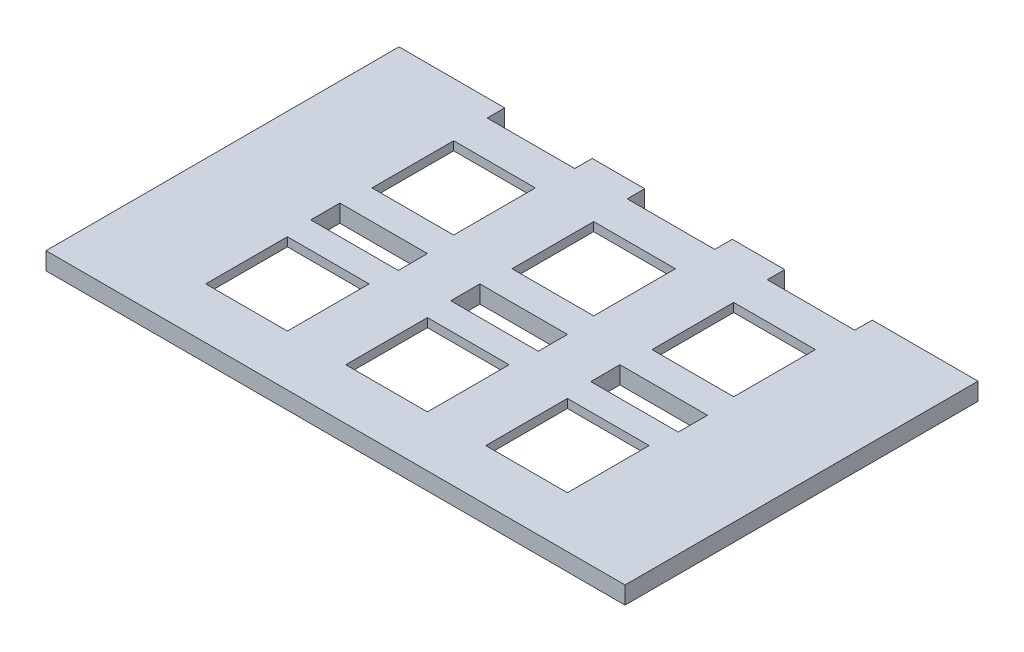
SolidWorks part; units mm, degrees
ref_plane "Front Plane" through (0, 0, 0) normal (0, 0, 1) x (1, 0, 0)
ref_plane "Top Plane" through (0, 0, 0) normal (0, 1, 0) x (1, 0, 0)
ref_plane "Right Plane" through (0, 0, 0) normal (1, 0, 0) x (0, 0, -1)
sketch "Sketch1" plane through (0, 0, 0) normal (0, 1, 0) x (1, 0, 0)
  line L1 (0, 0) -> (88.5, 0)
  line L2 (0, 0) -> (0, 60.5)
  line L3 (0, 60.5) -> (88.5, 60.5)
  line L4 (88.5, 0) -> (88.5, 60.5)
  dimension "D1" = 88.5
  dimension "D2" = 60.5
extrude "Boss-Extrude1" add sketch "Sketch1" along normal blind 3
sketch "Sketch2" plane through (88.5, 0, 0) normal (1, 0, 0) x (0, 0, -1)
  line L0 (0, 3) -> (60.5, 3) construction
  line L1 (2.3, 3) -> (58.2, 3)
  line L2 (2.3, 3) -> (2.3, 0)
  line L3 (2.3, 0) -> (58.2, 0)
  line L4 (58.2, 3) -> (58.2, 0)
  line L5 (0, 0) -> (60.5, 0) construction
  line L6 (0, 3) -> (0, 0) construction
  line L7 (60.5, 3) -> (60.5, 0) construction
  dimension "D1" = 2.3
  dimension "D2" = 2.3
extrude "Boss-Extrude2" add sketch "Sketch2" along normal blind 5.375
ref_plane "Plane1" through (44.25, 0, 0) normal (1, 0, 0) x (0, 0, -1)
mirror "Mirror2" about plane through (44.25, 0, 0) normal (1, 0, 0) of "Boss-Extrude2"
sketch "Sketch3" plane through (0, 0, 0) normal (0, -1, 0) x (1, 0, 0)
  line L0 (44.25, 0) -> (44.25, -60.5) construction
  line L1 (0, 0) -> (88.5, 0) construction
  line L2 (88.5, -60.5) -> (0, -60.5) construction
  line L3 (-5, -44.25) -> (90.6, -44.25) construction
  line L6 (44.25, -30.25) -> (50.6737, -30.25) construction
  line L7 (13.25, -51.25) -> (27.25, -51.25)
  line L8 (13.25, -51.25) -> (13.25, -37.25)
  line L9 (13.25, -37.25) -> (27.25, -37.25)
  line L10 (27.25, -51.25) -> (27.25, -37.25)
  line L11 (13.25, -51.25) -> (27.25, -37.25) construction
  line L12 (13.25, -37.25) -> (27.25, -51.25) construction
  line L13 (47.4618, -30.25) -> (47.4618, -60.5) construction
  line L14 (47.4618, -30.25) -> (47.4618, 0) construction
  line L15 (47.4618, -15.125) -> (44.25, -15.125) construction
  line L16 (47.4618, -45.375) -> (44.25, -45.375) construction
  point P12 (20.25, -44.25)
  dimension "D1" = 14
  dimension "D2" = 14
  dimension "D3" = 24
  dimension "D4" = 14
ref_plane "Plane2" through (0, 0, -30.25) normal (0, 0, -1) x (-1, 0, 0)
ref_axis "Axis1" through (44.25, -0.15, -30.25) along (0, 1, 0)
extrude "Cut-Extrude4" cut sketch "Sketch3" against normal through all
sketch "Sketch7" plane through (0, 0, 0) normal (0, -1, 0) x (1, 0, 0)
  line L0 (13.25, -44.25) -> (27.25, -44.25) construction
  line L1 (13.25, -37.25) -> (27.25, -37.25) construction
  line L2 (13.25, -37.25) -> (13.25, -51.25) construction
  line L3 (13.25, -51.25) -> (27.25, -51.25) construction
  line L4 (27.25, -37.25) -> (27.25, -51.25) construction
  line L5 (20.25, -37.25) -> (20.25, -51.25) construction
  line L7 (10.25, -54.25) -> (30.25, -54.25)
  line L8 (10.25, -54.25) -> (10.25, -34.25)
  line L9 (10.25, -34.25) -> (30.25, -34.25)
  line L10 (30.25, -54.25) -> (30.25, -34.25)
  line L11 (10.25, -54.25) -> (30.25, -34.25) construction
  line L12 (10.25, -34.25) -> (30.25, -54.25) construction
  point P10 (20.25, -44.25)
  dimension "D1" = 20
  dimension "D2" = 20
extrude "Cut-Extrude5" cut sketch "Sketch7" against normal offset from surface (1.5 mm away) 1.5 up to face at (20.25, 3, -44.25)
mirror "Mirror4" about plane through (44.25, 0, 0) normal (1, 0, 0) of "Cut-Extrude5", "Cut-Extrude4"
sketch "Sketch9" plane through (0, 0, -60.5) normal (0, 0, -1) x (-1, 0, 0)
  line L0 (-88.5, 3) -> (0, 3) construction
  line L1 (-12.75, 3) -> (-27.75, 3)
  line L2 (-12.75, 3) -> (-12.75, 0)
  line L3 (-12.75, 0) -> (-27.75, 0)
  line L4 (-27.75, 3) -> (-27.75, 0)
  line L5 (-88.5, 0) -> (0, 0) construction
  line L6 (-44.25, 3) -> (-44.25, 0) construction
  dimension "D1" = 15
  dimension "D2" = 16.5
extrude "Cut-Extrude6" cut sketch "Sketch9" against normal blind 3
mirror "Mirror6" about plane through (44.25, 0, 0) normal (1, 0, 0) of "Cut-Extrude6"
sketch "Sketch10" plane through (0, 3, 0) normal (0, 1, 0) x (1, 0, 0)
  line L0 (27.25, 51.25) -> (61.25, 51.25) construction
  line L1 (27.25, 37.25) -> (61.25, 37.25) construction
  line L3 (37.25, 51.25) -> (51.25, 51.25)
  line L4 (37.25, 51.25) -> (37.25, 37.25)
  line L5 (37.25, 37.25) -> (51.25, 37.25)
  line L6 (51.25, 51.25) -> (51.25, 37.25)
  point P12 (44.25, 51.25)
  point P13 (44.25, 51.25)
  dimension "D1" = 14
extrude "Cut-Extrude7" cut sketch "Sketch10" against normal blind 10
sketch "Sketch11" plane through (0, 0, 0) normal (0, -1, 0) x (1, 0, 0)
  line L0 (44.25, -37.25) -> (44.25, -51.25) construction
  line L1 (51.25, -37.25) -> (37.25, -37.25) construction
  line L2 (37.25, -51.25) -> (51.25, -51.25) construction
  line L4 (34.25, -34.25) -> (54.25, -34.25)
  line L5 (34.25, -34.25) -> (34.25, -54.25)
  line L6 (34.25, -54.25) -> (54.25, -54.25)
  line L7 (54.25, -34.25) -> (54.25, -54.25)
  line L8 (34.25, -34.25) -> (54.25, -54.25) construction
  line L9 (34.25, -54.25) -> (54.25, -34.25) construction
  point P6 (44.25, -44.25)
  dimension "D1" = 20
extrude "Cut-Extrude8" cut sketch "Sketch11" against normal blind 1.5
sketch "Sketch12" plane through (0, 0, 0) normal (0, -1, 0) x (1, 0, 0)
  line L0 (60.75, -60.5) -> (27.75, -60.5) construction
  line L1 (36.75, -60.5) -> (51.75, -60.5)
  line L2 (36.75, -60.5) -> (36.75, -57.5)
  line L3 (36.75, -57.5) -> (51.75, -57.5)
  line L4 (51.75, -60.5) -> (51.75, -57.5)
  line L5 (60.75, -57.5) -> (75.75, -57.5) construction
  line L6 (44.25, -60.5) -> (44.25, -51.25) construction
  line L7 (51.25, -51.25) -> (37.25, -51.25) construction
  dimension "D1" = 15
extrude "Cut-Extrude9" cut sketch "Sketch12" against normal blind 40
ref_plane "Plane3" through (0, 0, -30) normal (0, 0, 1) x (1, 0, 0)
mirror "Mirror8" about plane through (0, 0, -30) normal (0, 0, 1) of "Cut-Extrude5", "Mirror4", "Cut-Extrude7", "Cut-Extrude8"
sketch "Sketch13" plane through (0, 3, 0) normal (0, 1, 0) x (1, 0, 0)
  line L0 (93.875, 58.2) -> (93.875, 2.3) construction
  line L1 (0, 58.2) -> (-5.375, 58.2)
  line L2 (0, 58.2) -> (0, 60.5)
  line L3 (0, 60.5) -> (-5.375, 60.5)
  line L4 (-5.375, 58.2) -> (-5.375, 60.5)
  line L5 (0, 2.3) -> (-5.375, 2.3)
  line L6 (0, 2.3) -> (0, 0)
  line L7 (0, 0) -> (-5.375, 0)
  line L8 (-5.375, 2.3) -> (-5.375, 0)
  line L9 (88.5, 2.3) -> (93.875, 2.3)
  line L10 (88.5, 2.3) -> (88.5, 0)
  line L11 (88.5, 0) -> (93.875, 0)
  line L12 (93.875, 2.3) -> (93.875, 0)
  line L13 (12.75, 60.5) -> (0, 60.5) construction
  line L14 (88.5, 58.2) -> (93.875, 58.2)
  line L15 (88.5, 58.2) -> (88.5, 60.5)
  line L16 (88.5, 60.5) -> (93.875, 60.5)
  line L17 (93.875, 58.2) -> (93.875, 60.5)
  line L18 (-5.375, 58.2) -> (-5.375, 2.3) construction
  line L19 (0, 0) -> (88.5, 0) construction
extrude "Boss-Extrude3" add sketch "Sketch13" against normal up to surface (3 mm away) up to face at (20.25, 0, -15.75)
sketch "Sketch15" plane through (0, 0, 0) normal (0, -1, 0) x (1, 0, 0)
  line L0 (20.25, -34.25) -> (20.25, -25.75) construction
  line L1 (10.25, -34.25) -> (30.25, -34.25) construction
  line L2 (30.25, -25.75) -> (10.25, -25.75) construction
  line L3 (20.25, -31.5) -> (83.6104, -31.5) construction
  line L8 (10.25, -25.75) -> (30.25, -25.75) construction
  line L9 (12.75, -27.25) -> (27.75, -27.25)
  line L10 (12.75, -27.25) -> (12.75, -32.25)
  line L11 (12.75, -32.25) -> (27.75, -32.25)
  line L12 (27.75, -27.25) -> (27.75, -32.25)
  line L13 (36.75, -27.25) -> (36.75, -32.25)
  line L14 (36.75, -27.25) -> (51.75, -27.25)
  line L15 (51.75, -27.25) -> (51.75, -32.25)
  line L16 (36.75, -32.25) -> (51.75, -32.25)
  line L17 (44.25, -31.5) -> (107.6104, -31.5) construction
  line L18 (60.75, -27.25) -> (60.75, -32.25)
  line L19 (60.75, -27.25) -> (75.75, -27.25)
  line L20 (75.75, -27.25) -> (75.75, -32.25)
  line L21 (60.75, -32.25) -> (75.75, -32.25)
  line L22 (68.25, -31.5) -> (131.6104, -31.5) construction
  point P10 (20.25, -27.25)
  dimension "D1" = 15
  dimension "D2" = 5
  dimension "D3" = 1.5
  dimension "D4" = 3
extrude "Cut-Extrude11" cut sketch "Sketch15" against normal through all
